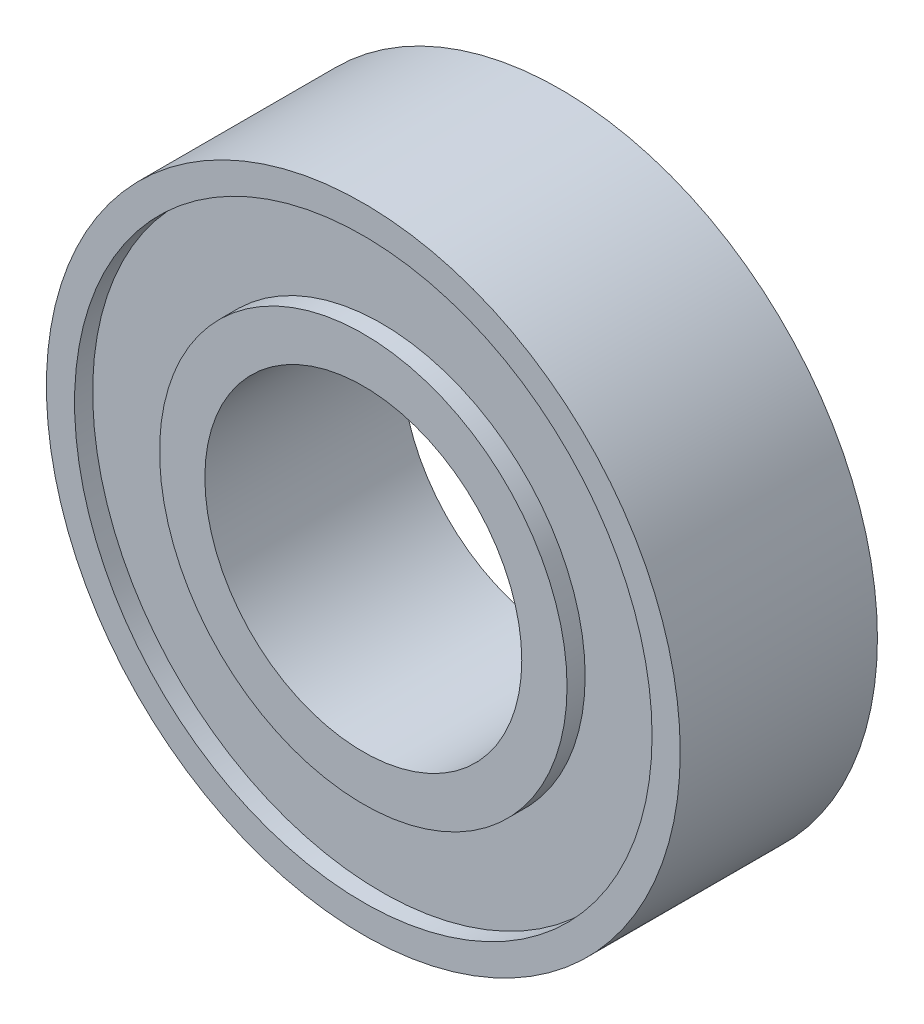
SolidWorks part; units mm, degrees
ref_plane "Front Plane" through (0, 0, 0) normal (0, 0, 1) x (1, 0, 0)
ref_plane "Top Plane" through (0, 0, 0) normal (0, 1, 0) x (1, 0, 0)
ref_plane "Right Plane" through (0, 0, 0) normal (1, 0, 0) x (0, 0, -1)
sketch "Sketch1" plane through (0, 0, 0) normal (0, 0, 1) x (1, 0, 0)
  circle A0 centre (0, 0) radius 8.001
  circle A1 centre (0, 0) radius 4.0005
  dimension "D1" = 16.002
  dimension "D2" = 8.001
extrude "Boss-Extrude1" add sketch "Sketch1" along normal blind 4.9784
sketch "Sketch2" plane through (0, 0, 4.9784) normal (0, 0, 1) x (1, 0, 0)
  circle A0 centre (0, 0) radius 5.1435
  circle A1 centre (0, 0) radius 7.2898
  circle A2 centre (0, 0) radius 4.0005 construction
  circle A3 centre (0, 0) radius 8.001 construction
  dimension "D1" = 1.143
  dimension "D2" = 0.7112
extrude "Cut-Extrude1" cut sketch "Sketch2" against normal blind 0.4572
sketch "Sketch3" plane through (0, 0, 0) normal (0, 0, -1) x (-1, 0, 0)
  circle A0 centre (0, 0) radius 7.2898
  circle A1 centre (0, 0) radius 5.1435
  circle A2 centre (0, 0) radius 5.1435 construction
  circle A3 centre (0, 0) radius 7.2898 construction
extrude "Cut-Extrude2" cut sketch "Sketch3" against normal blind 0.4572
ref_axis "Axis1" through (0, 0, 12.0691) along (0, 0, -1)
